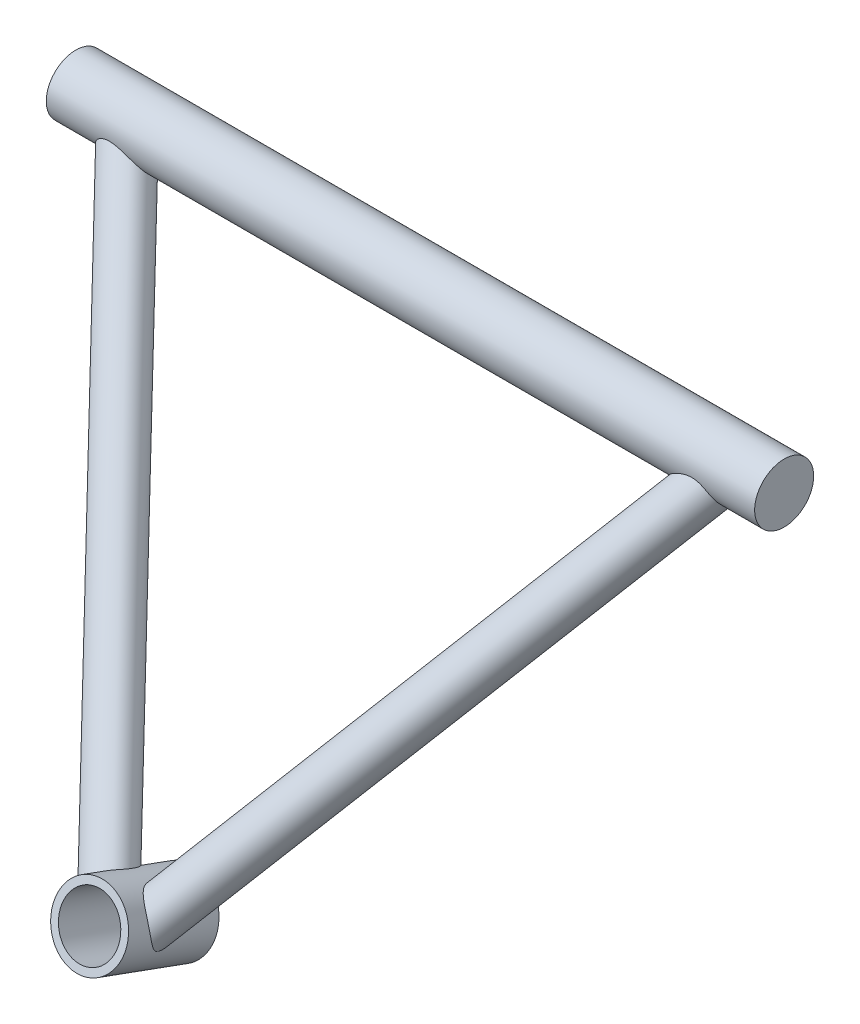
SolidWorks part; units mm, degrees
material "AISI 4130 Steel, normalized at 870C"
ref_plane "Front Plane" through (0, 0, 0) normal (0, 0, 1) x (1, 0, 0)
ref_plane "Top Plane" through (0, 0, 0) normal (0, 1, 0) x (1, 0, 0)
ref_plane "Right Plane" through (0, 0, 0) normal (1, 0, 0) x (0, 0, -1)
sketch "Sketch3" plane through (0, 0, 0) normal (0, 1, 0) x (1, 0, 0)
  line L0 (-5.08, -6.35) -> (5.08, -6.35) construction
  line L2 (0, -88.2205) -> (0, 88.2205) construction
  line L3 (5.08, 0) -> (-5.08, 0) construction
  dimension "D1" = 5.08
  dimension "D2" = 10.16
  dimension "D3" = 6.35
  dimension "D4" = 10.16
  dimension "D5" = 5.08
ref_plane "Plane1" through (0, 3.0807, 3.9431) normal (0, 0.6157, 0.788) x (1, 0, 0)
ref_plane "Plane3" through (0, 0, 0) normal (0, 0.342, 0.9397) x (-1, 0, 0)
sketch "Sketch1" plane through (0, 0, 0) normal (0, 0.342, 0.9397) x (1, 0, 0)
  circle A0 centre (0, 0) radius 15.875
  dimension "D1" = 31.75
extrude "Boss-Extrude1" add sketch "Sketch1" along normal mid plane 41.402 contours A0
sketch "Sketch4" plane through (0, 3.0807, 3.9431) normal (0, 0.6157, 0.788) x (1, 0, 0)
  line L0 (-5.08, -3.9095) -> (-128.905, 210.5617)
  line L2 (0, -90.5202) -> (0, 90.5202) construction
  dimension "D2" = 30
  dimension "D3" = 247.65
sweep "Sweep1" add path "Sketch4" circular profile diameter 19.05 parameters "D3"=19.05
sketch "Sketch15" plane through (0, 3.0807, 3.9431) normal (0, 0.6157, 0.788) x (1, 0, 0)
  line L0 (5.08, -3.9095) -> (128.905, 210.5617)
  line L1 (0, -90.5202) -> (0, 90.5202) construction
  dimension "D1" = 247.65
  dimension "D2" = 30
sweep "Sweep2" add path "Sketch15" circular profile diameter 19.05 parameters "D3"=19.05
sketch "Sketch36" plane through (-123.4022, 168.4285, -131.5907) normal (-0.5, 0.6824, -0.5332) x (0.8659, 0.3844, -0.32)
  circle A0 centre (-6.431, -4.9047) radius 7.9375
  dimension "D1" = 15.875
extrude "Cut-Extrude2" cut sketch "Sketch36" against normal up to surface (266.5251 mm away) up to face at (14.7828, 3.3132, -7.8163)
sketch "Sketch37" plane through (123.4022, 168.4285, -131.5907) normal (0.5, 0.6824, -0.5332) x (0.8659, -0.3844, 0.32)
  circle A0 centre (6.431, -4.9047) radius 7.9375
  dimension "D1" = 15.875
extrude "Cut-Extrude3" cut sketch "Sketch37" against normal up to surface (234.7454 mm away) up to face at (-0.1539, -14.1434, 7.5546)
sketch "Sketch77" plane through (0, 7.0802, 19.4526) normal (0, 0.342, 0.9397) x (1, 0, 0)
  circle A1 centre (0, 0) radius 15.875
extrude "Boss-Extrude2" add sketch "Sketch77" against normal up to surface (41.402 mm away) up to face at (0, -21.9978, -14.023)
sketch "Sketch2" plane through (0, -7.0802, -19.4526) normal (0, -0.342, -0.9397) x (-1, 0, 0)
  circle A0 centre (0, 0) radius 12.7
  dimension "D1" = 25.4
extrude "Cut-Extrude1" cut sketch "Sketch2" against normal up to next
ref_plane "Plane2" through (0, 0, -127) normal (0, 0, 1) x (1, 0, 0)
ref_plane "Plane4" through (0, 177.8, 0) normal (0, 1, 0) x (1, 0, 0)
sketch "Sketch40" plane through (-106.934, 0, -127) normal (0, 0, 1) x (1, 0, 0)
  line L0 (108.4431, 171.45) -> (50108.4431, 171.45) construction
  line L1 (-45.466, 171.45) -> (259.334, 171.45)
  point P0 (106.934, 171.45)
  point P1 (106.934, 171.45)
  dimension "D1" = 304.8
  dimension "D5" = 171.45
sweep "Sweep5" add path "Sketch40" circular profile diameter 25.4 parameters "D3"=25.4
